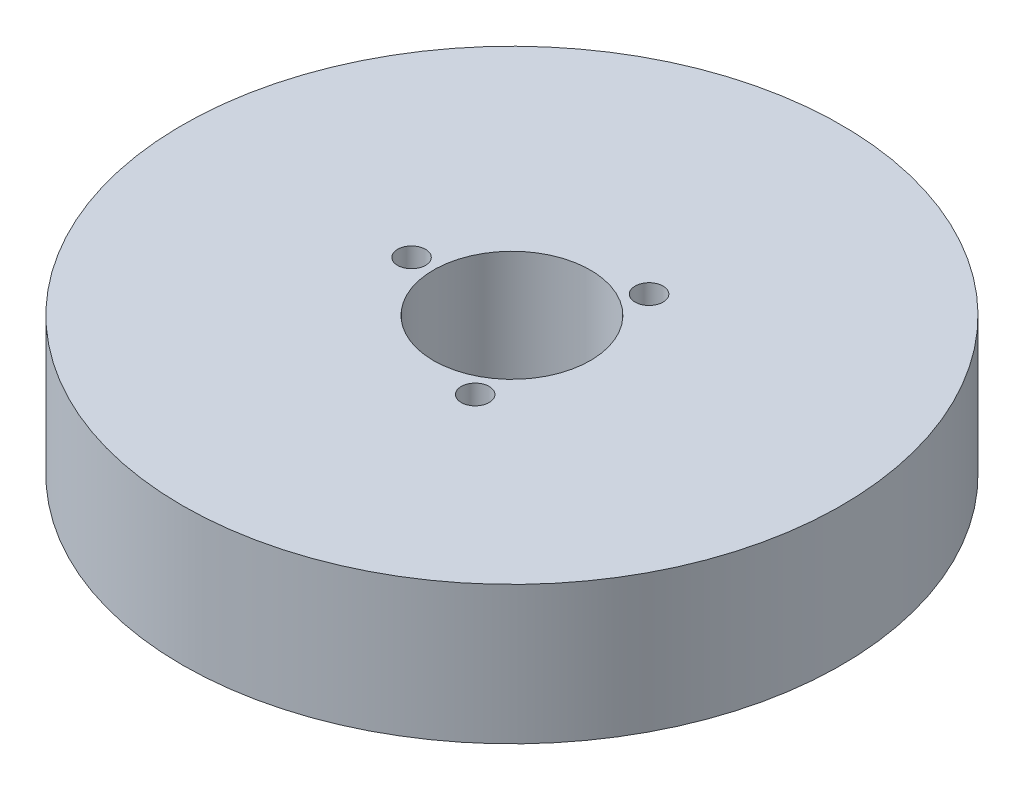
SolidWorks part; units mm, degrees
ref_plane "Front Plane" through (0, 0, 0) normal (0, 0, 1) x (1, 0, 0)
ref_plane "Top Plane" through (0, 0, 0) normal (0, 1, 0) x (1, 0, 0)
ref_plane "Right Plane" through (0, 0, 0) normal (1, 0, 0) x (0, 0, -1)
sketch "Sketch1" plane through (0, 0, 0) normal (0, 1, 0) x (1, 0, 0)
  circle A0 centre (0, 0) radius 52.5
  dimension "FLANGE_OD" = 105
extrude "Boss-Extrude1" add sketch "Sketch1" along normal blind 22
sketch "Sketch2" plane through (0, 0, 0) normal (0, 1, 0) x (1, 0, 0)
  circle A0 centre (0, 0) radius 12.5
  dimension "BORE_D" = 25
extrude "Cut-Extrude1" cut sketch "Sketch2" along normal through all
sketch "Sketch3" plane through (0, 22, 0) normal (0, 1, 0) x (1, 0, 0)
  circle A0 centre (0, 0) radius 15.9925 construction
  circle A1 centre (-15.9925, 0) radius 2.226
  dimension "BOLT_D" = 4.4521
  dimension "BOLT_PCD" = 31.9851
extrude "Cut-Extrude2" cut sketch "Sketch3" against normal blind 15.4313
pattern_circular "CirPattern1" count 3 over 360 about axis through (0, 0, 0) along (0, 1, 0) of "Cut-Extrude2"
